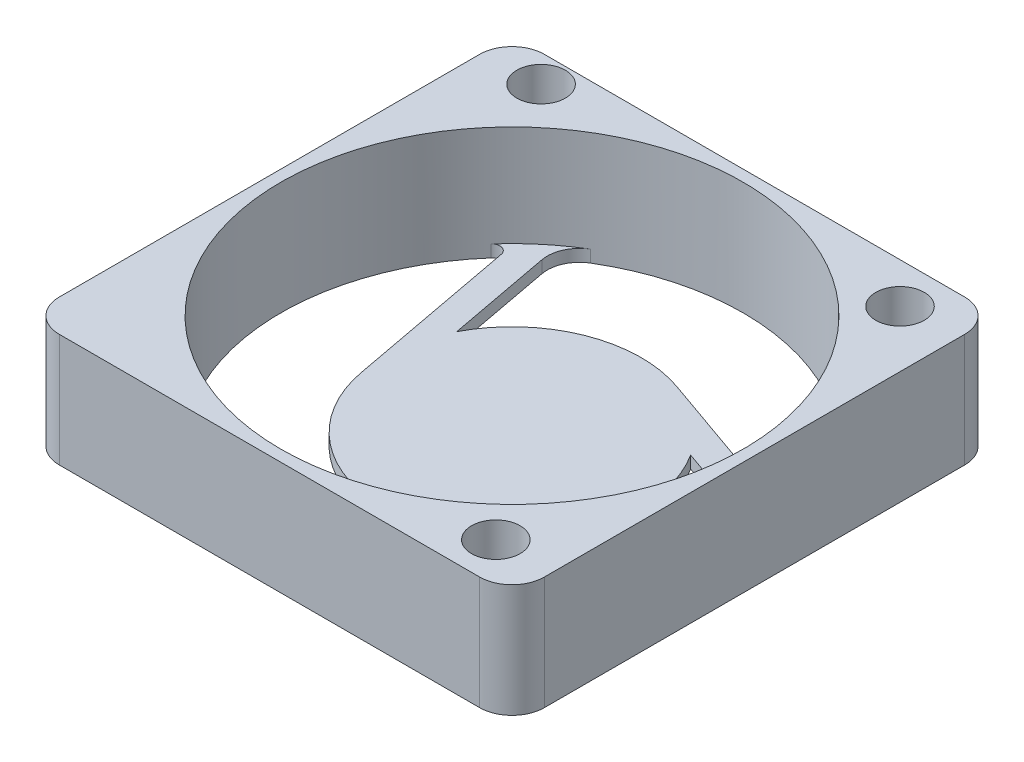
SolidWorks part; units mm, degrees
ref_plane "Front" through (0, 0, 0) normal (0, 0, 1) x (1, 0, 0)
ref_plane "Top" through (0, 0, 0) normal (0, 1, 0) x (1, 0, 0)
ref_plane "Right" through (0, 0, 0) normal (1, 0, 0) x (0, 0, -1)
sketch "Sketch1" plane through (0, 0, 0) normal (0, 1, 0) x (1, 0, 0)
  line L0 (-50, 0) -> (50, 0) construction
  line L1 (-13, -15) -> (13, -15)
  line L2 (-15, -13) -> (-15, 13)
  line L3 (-13, 15) -> (13, 15)
  line L4 (15, -13) -> (15, 13)
  line L5 (-15, 0) -> (0, 0) construction
  line L6 (0, 0) -> (0, 15) construction
  circle A0 centre (-11.5, 13.3) radius 1.5
  circle A1 centre (11.5, 12.5) radius 1.5
  circle A2 centre (11.5, -12.5) radius 1.5
  circle A3 centre (-11.5, -13.3) radius 1.5 construction
  arc A4 (13, -15) -> (15, -13) centre (13, -13) ccw
  arc A5 (-13, -15) -> (-15, -13) centre (-13, -13) cw
  arc A6 (13, 15) -> (15, 13) centre (13, 13) cw
  arc A7 (-15, 13) -> (-13, 15) centre (-13, 13) cw
  point P0 (0, 0)
  point P19 (15, -15)
  point P24 (15, 15)
  point P27 (-15, 15)
  dimension "D7" = 2
  dimension "D8" = 3
  dimension "D9" = 3
  dimension "D6" = 0.8
  dimension "D3" = 23
  dimension "D5" = 25
  dimension "D4" = 11.5
  dimension "D1" = 30
  dimension "D2" = 30
extrude "MainBlock" add sketch "Sketch1" along normal blind 7
sketch "Sketch2" plane through (0, 7, 0) normal (0, 1, 0) x (1, 0, 0)
  circle A0 centre (0, 0) radius 14.3
  dimension "D1" = 28.6
extrude "RotorSpace" cut sketch "Sketch2" against normal blind 6.25
sketch "Sketch3" plane through (0, 0.75, 0) normal (0, 1, 0) x (1, 0, 0)
  line L0 (2.6526, 7.5474) -> (13.8349, 3.6174)
  line L1 (14.2001, 1.6871) -> (6.7405, 4.3088)
  line L2 (5.21, -6.0709) -> (-3.7847, -13.7901)
  line L3 (-5.639, -13.1412) -> (0.3613, -7.9918)
  line L4 (-7.8626, -1.4765) -> (-10.0502, 10.1727)
  line L5 (-8.5611, 11.4541) -> (-7.1018, 3.683)
  circle A0 centre (0, 0) radius 8
  circle A1 centre (0, 0) radius 14.3 construction
  point P19 (0, 0)
  point P21 (0, 0)
  dimension "D1" = 16
  dimension "D2" = 1.7
  dimension "D3" = 3
extrude "MotorBase" cut sketch "Sketch3" against normal up to surface (0.75 mm away)
fillet "Fillet1" radius 2 3 edges at (-8.5611, 0.375, -11.4541) (-5.639, 0.375, 13.1412) (14.2001, 0.375, -1.6871)
fillet "Fillet2" radius 0.5 3 edges at (-10.0502, 0.375, -10.1727) (13.8349, 0.375, -3.6174) (-3.7847, 0.375, 13.7901)
ref_plane "Plane1" through (0, 1.3, 0) normal (0, 1, 0) x (1, 0, 0)
